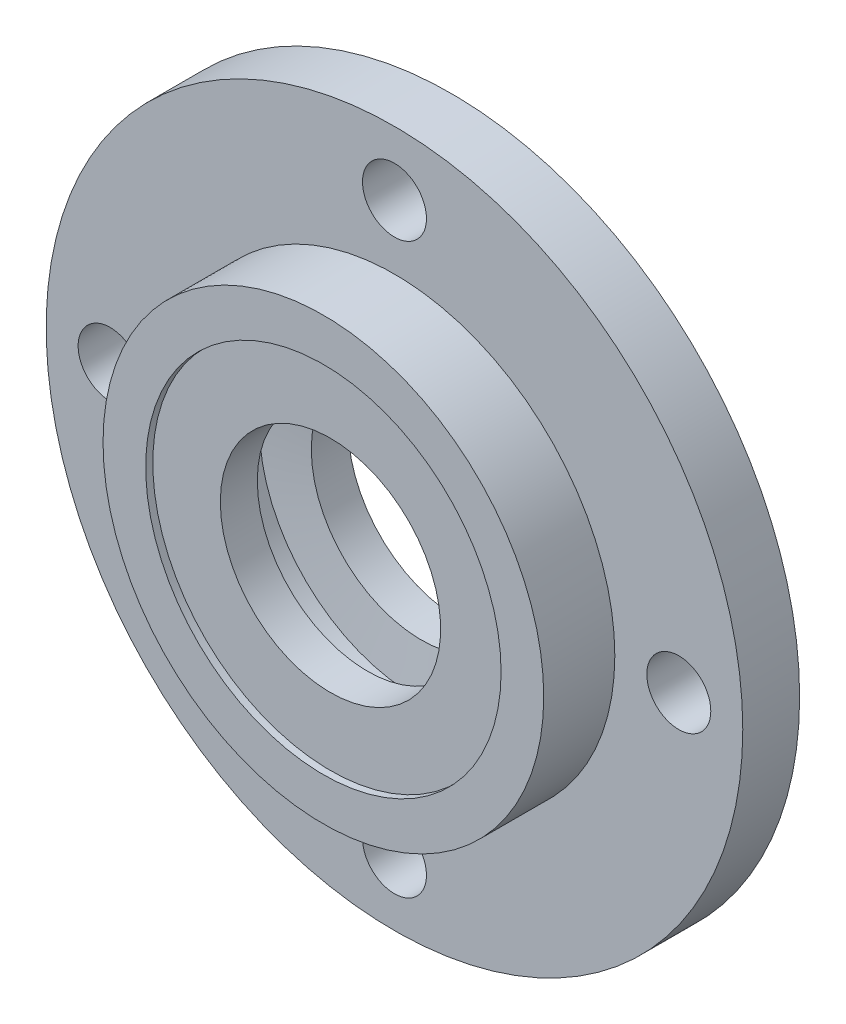
SolidWorks part; units mm, degrees
ref_plane "前视基准面" through (0, 0, 0) normal (0, 0, 1) x (1, 0, 0)
ref_plane "上视基准面" through (0, 0, 0) normal (0, 1, 0) x (1, 0, 0)
ref_plane "右视基准面" through (0, 0, 0) normal (1, 0, 0) x (0, 0, -1)
sketch "草图1" plane through (0, 0, 0) normal (0, 0, 1) x (1, 0, 0)
  circle A0 centre (0, 0) radius 30
extrude "凸台-拉伸1" add sketch "草图1" along normal blind 1
sketch "草图2" plane through (0, 0, 1) normal (0, 0, 1) x (1, 0, 0)
  circle A0 centre (0, 0) radius 49
extrude "凸台-拉伸2" add sketch "草图2" along normal blind 8
sketch "草图3" plane through (0, 0, 9) normal (0, 0, 1) x (1, 0, 0)
  circle A0 centre (0, 0) radius 31
extrude "凸台-拉伸3" add sketch "草图3" along normal blind 10
sketch "草图4" plane through (0, 0, 19) normal (0, 0, 1) x (1, 0, 0)
  circle A0 centre (0, 0) radius 25
extrude "切除-拉伸1" cut sketch "草图4" against normal blind 1
sketch "草图5" plane through (0, 0, 0) normal (0, 0, -1) x (-1, 0, 0)
  circle A0 centre (0, 0) radius 15.5
extrude "切除-拉伸2" cut sketch "草图5" against normal blind 6
sketch "草图6" plane through (0, 0, 6) normal (0, 0, -1) x (-1, 0, 0)
  circle A0 centre (0, 0) radius 22
extrude "切除-拉伸3" cut sketch "草图6" against normal blind 6
sketch "草图7" plane through (0, 0, 12) normal (0, 0, -1) x (-1, 0, 0)
  circle A0 centre (0, 0) radius 15.5
extrude "切除-拉伸4" cut sketch "草图7" against normal blind 6
chamfer "倒角1" distance 6.5 angle 7 1 edges at (-15.5, 0, 6) first distance on face at (-22, 0, 6)
chamfer "倒角2" distance 6.5 angle 7 1 edges at (-15.5, 0, 12) first distance on face at (-15.5, 0, 12)
sketch "草图8" plane through (0, 0, 9) normal (0, 0, 1) x (1, 0, 0)
  circle A0 centre (0, 40) radius 4.5
  circle A1 centre (40, 0) radius 4.5
  circle A2 centre (0, -40) radius 4.5
  circle A3 centre (-40, 0) radius 4.5
extrude "切除-拉伸5" cut sketch "草图8" against normal blind 10
